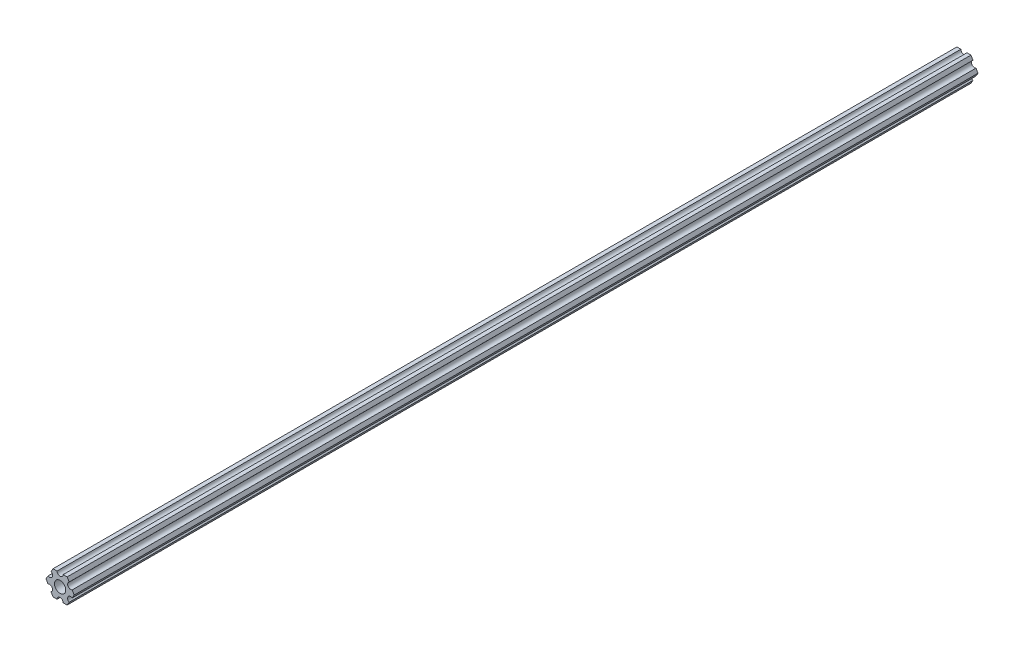
SolidWorks part; units mm, degrees
material "6061-T6 (SS)"
ref_plane "Front Plane" through (0, 0, 0) normal (0, 0, 1) x (1, 0, 0)
ref_plane "Top Plane" through (0, 0, 0) normal (0, 1, 0) x (1, 0, 0)
ref_plane "Right Plane" through (0, 0, 0) normal (1, 0, 0) x (0, 0, -1)
sketch "Sketch1" plane through (0, 0, 0) normal (0, 0, 1) x (1, 0, 0)
  line L0 (-4.7055, -4.5498) -> (-3.6662, -6.35)
  line L1 (-3.6662, -6.35) -> (-1.5875, -6.35)
  line L2 (1.5875, -6.35) -> (3.6662, -6.35)
  line L3 (3.6662, -6.35) -> (4.7055, -4.5498)
  line L4 (6.293, -1.8002) -> (7.3323, 0)
  line L5 (7.3323, 0) -> (6.293, 1.8002)
  line L6 (4.7055, 4.5498) -> (3.6662, 6.35)
  line L7 (3.6662, 6.35) -> (1.5875, 6.35)
  line L8 (-1.5875, 6.35) -> (-3.6662, 6.35)
  line L9 (-3.6662, 6.35) -> (-4.7055, 4.5498)
  line L10 (-6.293, 1.8002) -> (-7.3323, 0)
  line L11 (-7.3323, 0) -> (-6.293, -1.8002)
  circle A0 centre (0, 0) radius 2.9337
  arc A1 (-6.293, -1.8002) -> (-4.7055, -4.5498) centre (-5.4993, -3.175) cw
  arc A2 (-1.5875, -6.35) -> (1.5875, -6.35) centre (0, -6.35) cw
  arc A3 (4.7055, -4.5498) -> (6.293, -1.8002) centre (5.4993, -3.175) cw
  arc A4 (6.293, 1.8002) -> (4.7055, 4.5498) centre (5.4993, 3.175) cw
  arc A5 (1.5875, 6.35) -> (-1.5875, 6.35) centre (0, 6.35) cw
  arc A6 (-4.7055, 4.5498) -> (-6.293, 1.8002) centre (-5.4993, 3.175) cw
extrude "Boss-Extrude1" add sketch "Sketch1" against normal mid plane 469.9
